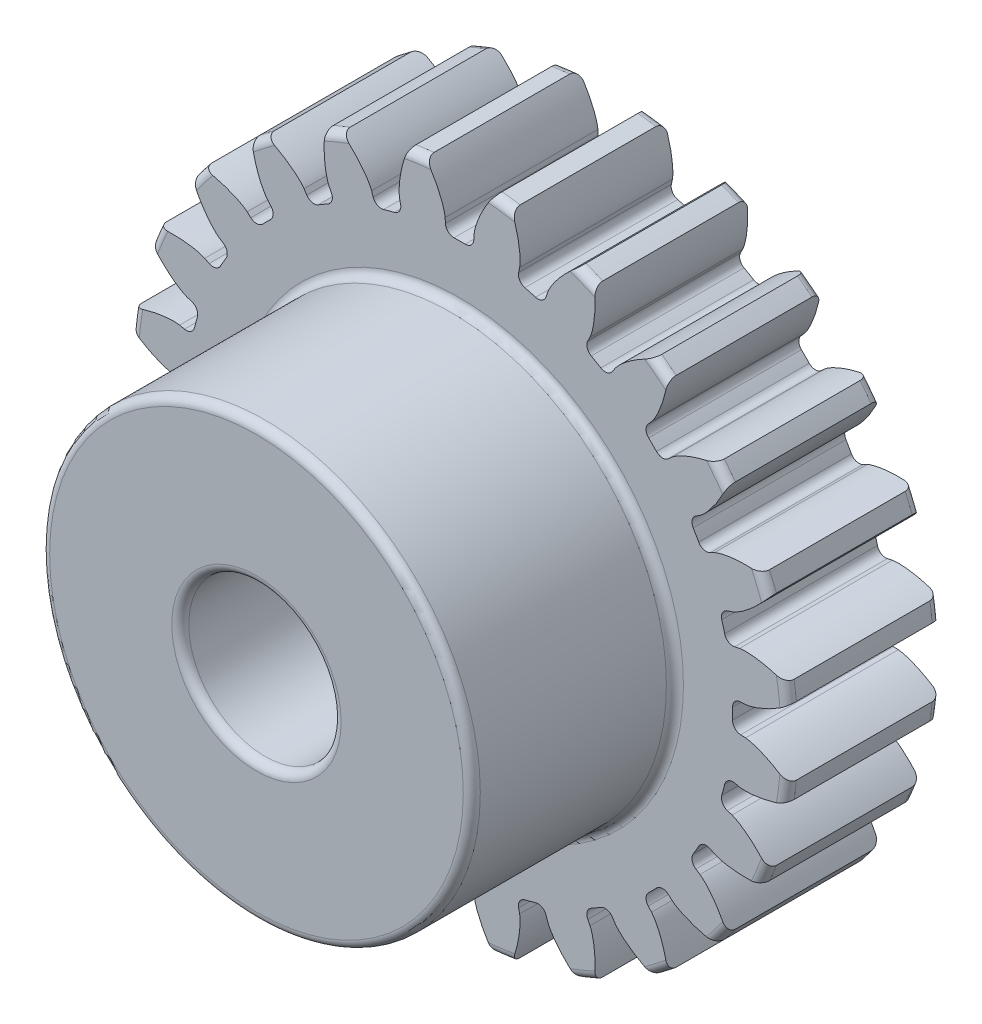
SolidWorks part; units mm, degrees
ref_plane "Front Plane" through (0, 0, 0) normal (0, 0, 1) x (1, 0, 0)
ref_plane "Top Plane" through (0, 0, 0) normal (0, 1, 0) x (1, 0, 0)
ref_plane "Right Plane" through (0, 0, 0) normal (1, 0, 0) x (0, 0, -1)
sketch "Sketch1" plane through (0, 0, 0) normal (0, 0, 1) x (1, 0, 0)
  line L0 (0, 0) -> (0, 9.525) construction
  line L1 (-3.0613, 10.6392) -> (3.0613, 8.4108) construction
  circle A0 centre (0, 0) radius 8.5328 construction
  circle A1 centre (0, 0) radius 10.3187 construction
  circle A2 centre (0, 0) radius 9.525 construction
  circle A3 centre (0, 0) radius 8.9506 construction
  circle A4 centre (0, 0) radius 2.3813 construction
  circle A5 centre (0, 0) radius 6.731 construction
  point P8 (406.4, 0)
  point P13 (304.8, 0)
  dimension "OD | Outside Diameter" = 20.6375
  dimension "Root Diameter" = 17.0656
  dimension "Gear Pitch Diameter" = 19.05
  dimension "Base Diameter" = 17.9011
  dimension "For Shaft Diameter" = 4.7625
  dimension "Hub Diameter" = 13.462
  dimension "Pressure Angle" = 20
  dimension "Number of Teeth" = 609.6
  dimension "Gear Pitch | Diametral Pitch" = 812.8
sketch "Sketch2" plane through (0, 0, 0) normal (1, 0, 0) x (0, 0, -1)
  line L0 (-5.5626, 0) -> (5.5626, 0) construction
  line L1 (-5.5626, 10.3187) -> (5.5626, 10.3188) construction
  point P2 (0, 10.3187)
  point P4 (0.7874, 0)
  point P6 (0.7874, 10.3187)
  dimension "Overall Width" = 11.1252
  dimension "Hub Width" = 6.35
  dimension "Face Width" = 4.7752
sketch "Sketch3" plane through (0, 0, 0) normal (0, 0, 1) x (1, 0, 0)
  circle A0 centre (0, 0) radius 10.3187
  circle A1 centre (0, 0) radius 10.3187 construction
extrude "Boss-Extrude1" add sketch "Sketch3" against normal up to vertex (5.5626 mm away) and the other way up to vertex (5.5626 mm away) up to point (0, 0, -5.5626) other way up to point (0, 0, 5.5626)
sketch "Sketch5" plane through (0, 0, 0) normal (1, 0, 0) x (0, 0, -1)
  line L1 (-5.5626, 10.3187) -> (0.7874, 10.3187)
  line L2 (-5.5626, 10.3187) -> (-5.5626, 6.731)
  line L3 (-5.5626, 6.731) -> (0.7874, 6.731)
  line L4 (0.7874, 10.3187) -> (0.7874, 6.731)
  line L11 (5.5626, 2.3813) -> (-5.5626, 2.3812)
  line L12 (5.5626, 2.3813) -> (5.5626, 0)
  line L13 (5.5626, 0) -> (-5.5626, 0)
  line L14 (-5.5626, 2.3812) -> (-5.5626, 0)
  point P5 (0, 2.3813)
  point P12 (0, 6.731)
revolve "Cut-Revolve1" cut sketch "Sketch5" angle 360 about L0
fillet "Fillet2" radius 0.2663 6 edges at (10.3187, 0, -5.5626) (2.3813, 0, -5.5626) (2.3812, 0, 5.5626) (6.731, 0, -0.7874) (10.3187, 0, -0.7874) (6.731, 0, 5.5626)
sketch "Sketch4" plane through (0, 0, 0) normal (0, 0, 1) x (1, 0, 0)
  line L0 (0, 0) -> (8.5219, 0.4311) construction
  line L2 (0, 0) -> (8.5219, -0.4311) construction
  line L4 (8.5219, 0.4311) -> (8.9391, 0.4522)
  line L5 (8.9391, -0.4522) -> (8.5219, -0.4311)
  arc A0 (8.5219, 0.4311) -> (8.5219, -0.4311) centre (0, 0) cw
  arc A3 (10.2637, 1.0648) -> (10.2637, -1.0648) centre (0, 0) cw
  circle A4 centre (0, 0) radius 10.3187 construction
  spline S0 degree 4 poles (8.9391, 0.4522) (8.9413, 0.4524) (8.9474, 0.4528) (8.9589, 0.454) (8.9776, 0.4564) (9.0014, 0.4602) (9.0321, 0.4658) (9.0682, 0.4734) (9.1076, 0.4828) (9.1505, 0.4942) (9.1931, 0.5065) (9.2354, 0.5197) (9.2775, 0.5336) (9.3282, 0.5515) (9.3889, 0.5743) (9.4594, 0.603) (9.539, 0.6378) (9.6195, 0.6757) (9.6984, 0.715) (9.7775, 0.7571) (9.8537, 0.7994) (9.9322, 0.8457) (10.0044, 0.8897) (10.0846, 0.9415) (10.1492, 0.9841) (10.2335, 1.0431) (10.2831, 1.0787) (10.3409, 1.1213) (10.3664, 1.1408) (10.3821, 1.1527) knots 0 0 0 0 0 0.005377 0.015084 0.028532 0.04661 0.064855 0.092111 0.119476 0.146842 0.174209 0.201575 0.228941 0.256307 0.307035 0.361767 0.4165 0.471232 0.525964 0.580697 0.635429 0.690161 0.744894 0.799626 0.854358 0.909091 0.954545 1 1 1 1 1 construction
  spline S1 degree 4 poles (8.9391, 0.4522) (8.9413, 0.4524) (8.9474, 0.4528) (8.9589, 0.454) (8.9776, 0.4564) (9.0014, 0.4602) (9.0321, 0.4658) (9.0682, 0.4734) (9.1076, 0.4828) (9.1505, 0.4942) (9.1931, 0.5065) (9.2354, 0.5197) (9.2775, 0.5336) (9.3282, 0.5515) (9.3889, 0.5743) (9.4594, 0.603) (9.539, 0.6378) (9.6195, 0.6757) (9.6984, 0.715) (9.7775, 0.7571) (9.8537, 0.7994) (9.9322, 0.8457) (10.0044, 0.8897) (10.0846, 0.9415) (10.1492, 0.9841) (10.2152, 1.0303) (10.2473, 1.0531) (10.2637, 1.0648) knots 0 0 0 0 0 0.005377 0.015084 0.028532 0.04661 0.064855 0.092111 0.119476 0.146842 0.174209 0.201575 0.228941 0.256307 0.307035 0.361767 0.4165 0.471232 0.525964 0.580697 0.635429 0.690161 0.744894 0.799626 0.854358 0.909091 0.909091 0.909091 0.909091 0.909091
  spline S2 degree 4 poles (8.9391, -0.4522) (8.9413, -0.4524) (8.9474, -0.4528) (8.9589, -0.454) (8.9776, -0.4564) (9.0014, -0.4602) (9.0321, -0.4658) (9.0682, -0.4734) (9.1076, -0.4828) (9.1505, -0.4942) (9.1931, -0.5065) (9.2354, -0.5197) (9.2775, -0.5336) (9.3282, -0.5515) (9.3889, -0.5743) (9.4594, -0.603) (9.539, -0.6378) (9.6195, -0.6757) (9.6984, -0.715) (9.7775, -0.7571) (9.8537, -0.7994) (9.9322, -0.8457) (10.0044, -0.8897) (10.0846, -0.9415) (10.1492, -0.9841) (10.2335, -1.0431) (10.2831, -1.0787) (10.3409, -1.1213) (10.3664, -1.1408) (10.3821, -1.1527) knots 0 0 0 0 0 0.005377 0.015084 0.028532 0.04661 0.064855 0.092111 0.119476 0.146842 0.174209 0.201575 0.228941 0.256307 0.307035 0.361767 0.4165 0.471232 0.525964 0.580697 0.635429 0.690161 0.744894 0.799626 0.854358 0.909091 0.954545 1 1 1 1 1 construction
  spline S3 degree 4 poles (8.9391, -0.4522) (8.9413, -0.4524) (8.9474, -0.4528) (8.9589, -0.454) (8.9776, -0.4564) (9.0014, -0.4602) (9.0321, -0.4658) (9.0682, -0.4734) (9.1076, -0.4828) (9.1505, -0.4942) (9.1931, -0.5065) (9.2354, -0.5197) (9.2775, -0.5336) (9.3282, -0.5515) (9.3889, -0.5743) (9.4594, -0.603) (9.539, -0.6378) (9.6195, -0.6757) (9.6984, -0.715) (9.7775, -0.7571) (9.8537, -0.7994) (9.9322, -0.8457) (10.0044, -0.8897) (10.0846, -0.9415) (10.1492, -0.9841) (10.2152, -1.0303) (10.2473, -1.0531) (10.2637, -1.0648) knots 0 0 0 0 0 0.005377 0.015084 0.028532 0.04661 0.064855 0.092111 0.119476 0.146842 0.174209 0.201575 0.228941 0.256307 0.307035 0.361767 0.4165 0.471232 0.525964 0.580697 0.635429 0.690161 0.744894 0.799626 0.854358 0.909091 0.909091 0.909091 0.909091 0.909091
  dimension "D1" = 17.0656
extrude "Cut-Extrude1" cut sketch "Sketch4" against normal through all both and the other way through all
fillet "Fillet1" radius 0.2663 2 edges at (8.5219, -0.4311, -3.175) (8.5219, 0.4311, -3.175)
pattern_circular "CirPattern1" count 24 over 360 about axis through (0, 0, 5.5626) along (0, 0, -1) of "Cut-Extrude1", "Fillet1"
ref_axis "Axis1" through (0, 0, -5.2963) along (0, 0, 1)
equation "\"Root Diameter@Sketch1\"=\"Root Diameter\""
equation "\"OD | Outside Diameter@Sketch1\"=\"Outside Diameter\""
equation "\"D1@CirPattern1\"=\"Number of Teeth\""
equation "\"Diametral Pitch\"=32"
equation "\"Number of Teeth\"= 24"
equation "\"Pressure Angle\"=20"
equation "\"Pitch Diameter\"= \"Number of Teeth\" / \"Diametral Pitch\""
equation "\"Base Diameter\"= \"Pitch Diameter\" * cos ( \"Pressure Angle\" )"
equation "\"Outside Diameter\"= ( \"Number of Teeth\" + 2 ) / \"Diametral Pitch\""
equation "\"Dedendum\"= 1.25 / \"Diametral Pitch\""
equation "\"Root Diameter\"= \"Pitch Diameter\" - ( 2 * \"Dedendum\" )"
equation "\"Pitch Angle\"= 360deg / \"Number of Teeth\""
equation "\"Alpha\"= sqr ( \"Pitch Diameter\" ^ 2 - \"Base Diameter\" ^ 2 ) / \"Base Diameter\" * 180 / PI - \"Pressure Angle\""
equation "\"Beta\"= ( \"Pitch Angle\" / 4 - \"Alpha\" )"
equation "\"Phi\"= sqr ( ( \"Outside Diameter\" / 2 ) ^ 2 - ( \"Base Diameter\" / 2 ) ^ 2 ) / ( \"Base Diameter\" / 2 )"
equation "\"Addendum\"= 1 / \"Diametral Pitch\""
equation "\"WorkingDepth\"= 2 / \"Diametral Pitch\""
equation "\"WholeDepth\"= 2.25 / \"Diametral Pitch\""
equation "\"Clearance\"= 0.25 / \"Diametral Pitch\""
equation "\"ToothThickness\"= ( pi * 2 ) / \"Diametral Pitch\""
equation "\"CircularPitch\"= pi / \"Diametral Pitch\""
equation "\"Number of Teeth@Sketch1\"=\"Number of Teeth\""
equation "\"Gear Pitch | Diametral Pitch@Sketch1\"=\"Diametral Pitch\""
equation "\"Pressure Angle@Sketch1\"=\"Pressure Angle\""
equation "\"Gear Pitch Diameter@Sketch1\"=\"Pitch Diameter\""
equation "\"Base Diameter@Sketch1\"=\"Base Diameter\""
equation "\"Fillet\"= \"Clearance\" * cos ( \"Pressure Angle\" ) * tan ( ( 90 + \"Pressure Angle\" ) / 2 )"
equation "\"D1@Fillet1\"=\"Fillet\""
equation "\"D1@Sketch4\"=if( \"Base Diameter\">\"Root Diameter\",\"Root Diameter\",\"Base Diameter\"-.00001)"
equation "\"D1@Fillet2\"=\"Fillet\""
